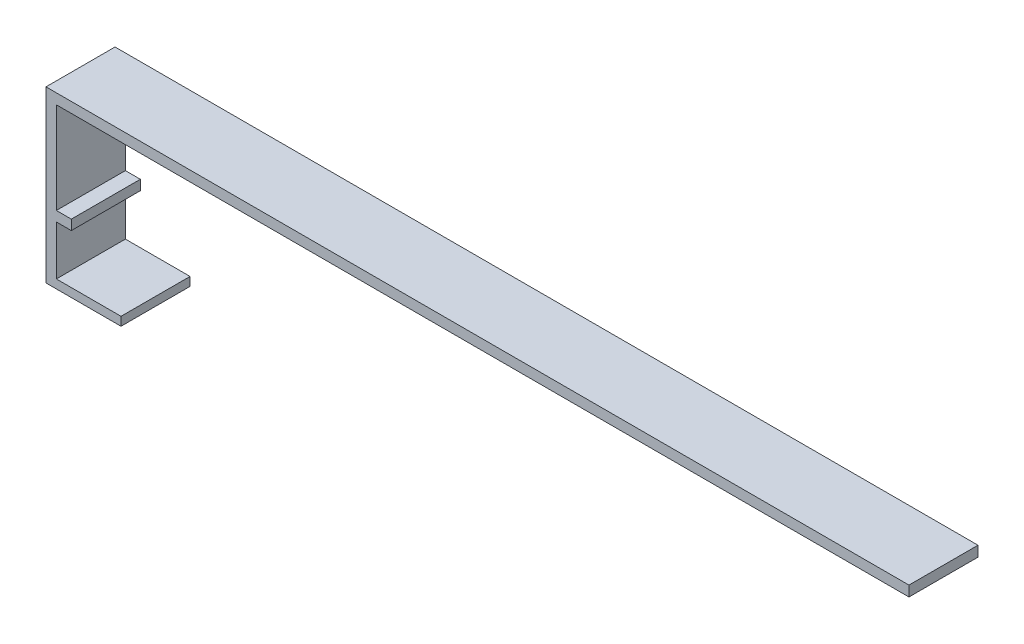
SolidWorks part; units mm, degrees
ref_plane "Front" through (0, 0, 0) normal (0, 0, 1) x (1, 0, 0)
ref_plane "Top" through (0, 0, 0) normal (0, 1, 0) x (1, 0, 0)
ref_plane "Right" through (0, 0, 0) normal (1, 0, 0) x (0, 0, -1)
sketch "Sketch1" plane through (0, 0, 0) normal (0, 1, 0) x (1, 0, 0)
  line L1 (0, 0) -> (250, 0)
  line L2 (0, 0) -> (0, 20)
  line L3 (0, 20) -> (250, 20)
  line L4 (250, 0) -> (250, 20)
  dimension "D1" = 250
  dimension "D2" = 20
extrude "Boss-Extrude1" add sketch "Sketch1" along normal blind 3
sketch "Sketch4" plane through (0, 0, -20) normal (0, 0, -1) x (-1, 0, 0)
  line L1 (0, 0) -> (-3, 0)
  line L2 (0, 0) -> (0, -45.5382)
  line L3 (0, -45.5382) -> (-3, -45.5382)
  line L4 (-3, 0) -> (-3, -45.5382)
  line L6 (-3, -24) -> (-3, -26.6921)
  line M5 (-250, 0) -> (0, 0)
  dimension "D4" = 3
extrude "Boss-Extrude3" add sketch "Sketch4" against normal blind 20 contours L4 L3 L2 M5 | L4 region at (1.5, -22.7691, -20)
sketch "Sketch7" plane through (0, 0, 0) normal (0, 0, 1) x (1, 0, 0)
  line L0 (3, 0) -> (3, -45.5382) construction
  line L1 (9.3339, -26.52) -> (3, -26.52)
  line L2 (9.3339, -26.52) -> (9.3339, -29.3966)
  line L3 (9.3339, -29.3966) -> (3, -29.3966)
  line L4 (3, -26.52) -> (3, -29.3966)
extrude "Boss-Extrude4" add sketch "Sketch7" against normal blind 20
sketch "Sketch8" plane through (0, 0, -20) normal (0, 0, -1) x (-1, 0, 0)
  line L1 (-21.7312, -43.7) -> (0, -43.7)
  line L2 (-21.7312, -43.7) -> (-21.7312, -46.2083)
  line L3 (-21.7312, -46.2083) -> (0, -46.2083)
  line L4 (0, -43.7) -> (0, -46.2083)
extrude "Boss-Extrude6" add sketch "Sketch8" against normal blind 20
sketch "Sketch10" plane through (9.3339, 0, 0) normal (1, 0, 0) x (0, 0, -1)
  line L1 (0, -26.52) -> (21.1213, -26.52)
  line L2 (0, -26.52) -> (0, -30.104)
  line L3 (0, -30.104) -> (21.1213, -30.104)
  line L4 (21.1213, -26.52) -> (21.1213, -30.104)
extrude "Cut-Extrude3" cut sketch "Sketch10" against normal blind 2
